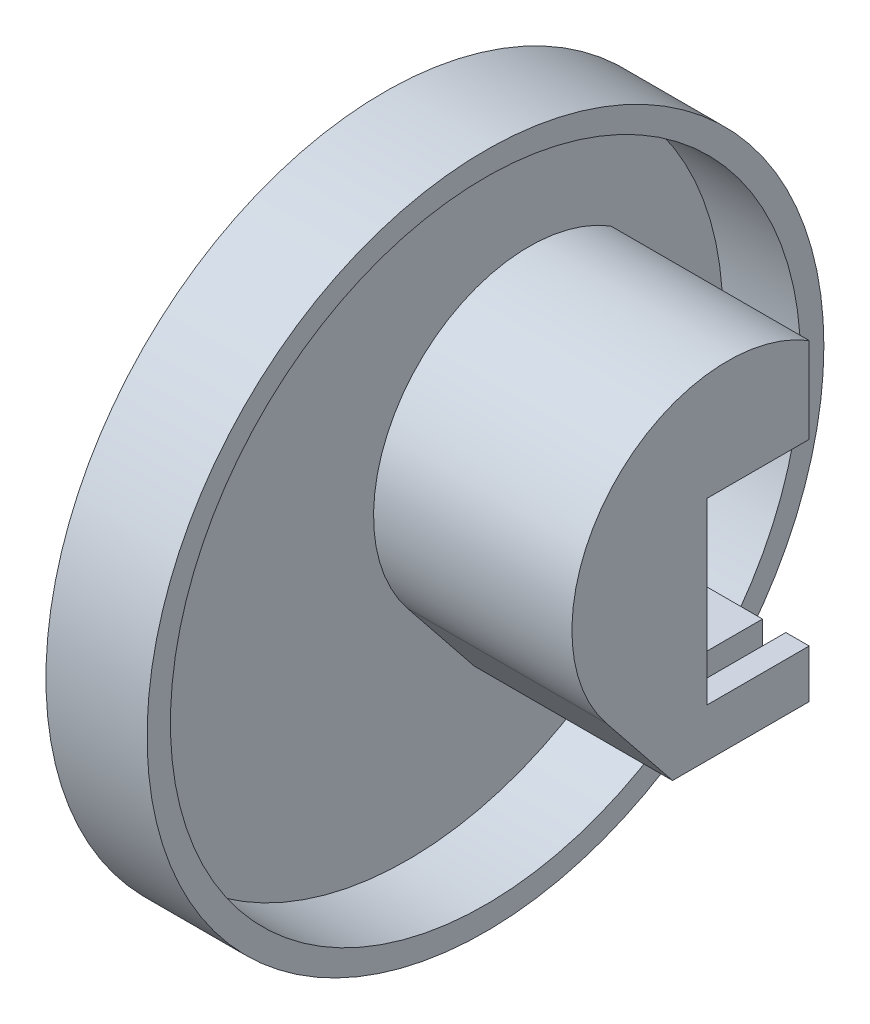
SolidWorks part; units mm, degrees
ref_plane "Plan de face" through (0, 0, 0) normal (0, 0, 1) x (1, 0, 0)
ref_plane "Plan de dessus" through (0, 0, 0) normal (0, 1, 0) x (1, 0, 0)
ref_plane "Plan de droite" through (0, 0, 0) normal (1, 0, 0) x (0, 0, -1)
sketch "Esquisse2" plane through (0, 0, 0) normal (1, 0, 0) x (0, 0, -1)
  circle A0 centre (0, 0) radius 40.5
  circle A1 centre (0, 0) radius 43.5
  dimension "D1" = 81
  dimension "D2" = 3
extrude "Boss.-Extru.1" add sketch "Esquisse2" along normal blind 10
extrude "Boss.-Extru.2" add sketch "Esquisse2<2>" against normal blind 3 contours A1
sketch "Esquisse2<2>" plane through (0, 0, 0) normal (1, 0, 0) x (0, 0, -1) same geometry as "Esquisse2"
sketch "Esquisse3" plane through (0, 0, 0) normal (1, 0, 0) x (0, 0, -1)
  line L0 (0, 12.5) -> (0, -12.5) construction
  line L2 (26.1112, 17.0229) -> (26.1112, 6.0229)
  line L3 (26.1112, 6.0229) -> (13, 6.0229)
  line L4 (13, 6.0229) -> (13, -16.9771)
  line L5 (13, -16.9771) -> (26.1112, -16.9771)
  line L6 (26.1112, -16.9771) -> (26.1112, -23.1771)
  line L7 (26.1112, -23.1771) -> (8.5486, -23.1771)
  line L8 (8.5486, -23.1771) -> (0, -12.5)
  line L9 (0, 0) -> (-4.3875, 0) construction
  line L10 (13, -16.9771) -> (13, -23.1771)
  line L11 (13, 6.0229) -> (13, 11.3229)
  line L12 (13, 11.3229) -> (26.1112, 11.3229)
  arc A0 (0, -12.5) -> (0, 12.5) centre (15.6125, 0) cw
  arc A2 (26.1112, 17.0229) -> (0, 12.5) centre (15.6125, 0) ccw
  arc A3 (13, -15.6771) -> (26.1112, 15.5229) centre (19.0599, 0.1312) cw
  dimension "D2" = 20
  dimension "D10" = 16.93
  dimension "D1" = 25
  dimension "D3" = 23
  dimension "D4" = 26.5
  dimension "D5" = 11
  dimension "D6" = 6.2
  dimension "D7" = 13
  dimension "D8" = 1.5
  dimension "D9" = 7.5
  dimension "D11" = 5.3
extrude "Boss.-Extru.3" add sketch "Esquisse3" along normal blind 12 contours L10 A3 L2 A2 A0 L8 L7 region at (0, 16.2729, -25.5826)
extrude "Boss.-Extru.4" add sketch "Esquisse3<3>" along normal blind 7.5 from surface contours L5 L10 L7 L6 | L10 A3 L2 A2 A0 L8 L7 | A3 L10 L4 L3 L2 | L12 L11 L3 L2 region at (0, 16.2729, -25.5826) region at (0, 3.1483, -10.8927) region at (0, 8.6729, -19.5556) region at (0, -20.0771, -19.5556) starting at face at (12, -4.0383, -9.7072)
sketch "Esquisse3<3>" plane through (0, 0, 0) normal (1, 0, 0) x (0, 0, -1) same geometry as "Esquisse3"
extrude "Boss.-Extru.5" add sketch "Esquisse3<4>" along normal blind 3 from surface contours A3 L4 L11 L12 L2 | L4 A3 L2 A2 A0 L8 L7 L10 region at (0, 16.2729, -25.5826) region at (0, 3.1483, -10.8927) starting at face at (19.5, -6.5939, -15.8211)
sketch "Esquisse3<4>" plane through (0, 0, 0) normal (1, 0, 0) x (0, 0, -1) same geometry as "Esquisse3"
extrude "Boss.-Extru.6" add sketch "Esquisse3<5>" along normal blind 3 from surface contours L5 L10 L7 L6 | L4 A3 L2 A2 A0 L8 L7 L10 | A3 L4 L11 L12 L2 | L12 L11 L3 L2 region at (0, 16.2729, -25.5826) region at (0, 3.1483, -10.8927) region at (0, 8.6729, -19.5556) region at (0, -20.0771, -19.5556) starting at face at (22.5, -1.3662, -12.3911)
sketch "Esquisse3<5>" plane through (0, 0, 0) normal (1, 0, 0) x (0, 0, -1) same geometry as "Esquisse3"
